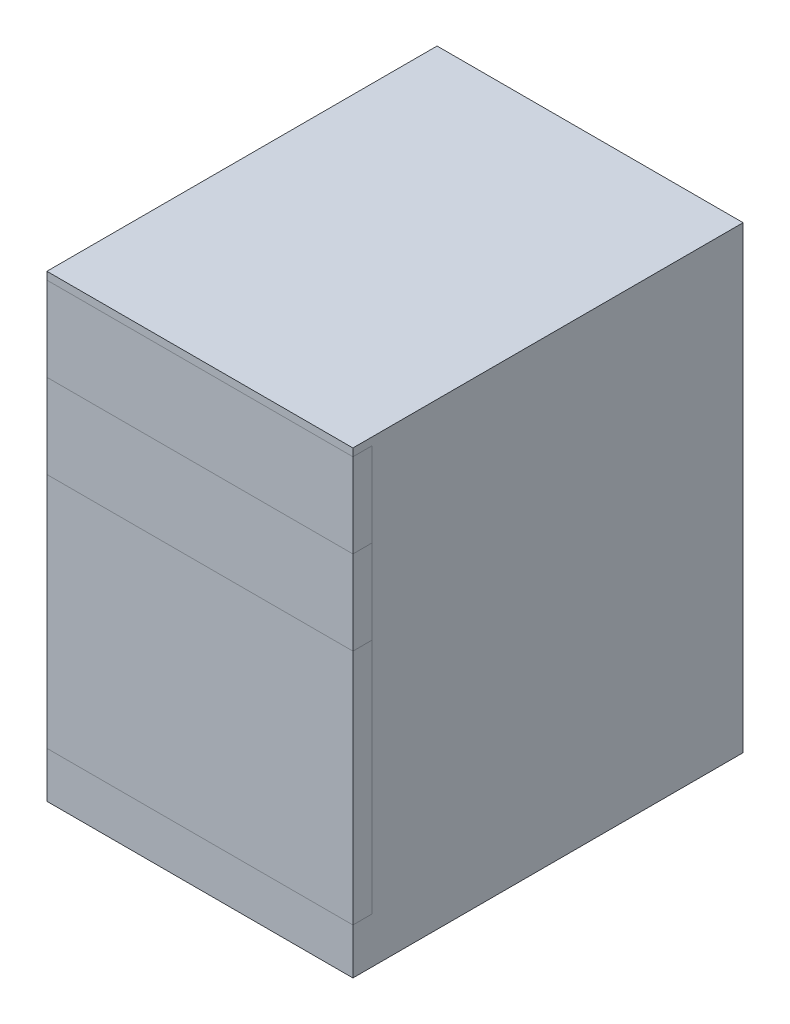
SolidWorks part; units mm, degrees
ref_plane "Front Plane" through (0, 0, 0) normal (0, 0, 1) x (1, 0, 0)
ref_plane "Top Plane" through (0, 0, 0) normal (0, 1, 0) x (1, 0, 0)
ref_plane "Right Plane" through (0, 0, 0) normal (1, 0, 0) x (0, 0, -1)
sketch "Sketch1" plane through (0, 0, 0) normal (0, 1, 0) x (1, 0, 0)
  line L1 (-200, -255) -> (200, -255)
  line L2 (-200, -255) -> (-200, 255)
  line L3 (-200, 255) -> (200, 255)
  line L4 (200, -255) -> (200, 255)
  line L5 (-200, -255) -> (200, 255) construction
  line L6 (-200, 255) -> (200, -255) construction
  point P0 (0, 0)
  dimension "D1" = 400
  dimension "D2" = 510
extrude "Boss-Extrude1" add sketch "Sketch1" along normal blind 600
sketch "Sketch2" plane through (0, 0, 255) normal (0, 0, 1) x (1, 0, 0)
  line L0 (200, 600) -> (200, 0) construction
  line L1 (-200, 600) -> (200, 600)
  line L2 (-200, 600) -> (-200, 590)
  line L3 (-200, 590) -> (200, 590)
  line L4 (200, 600) -> (200, 590)
  line L5 (-200, 600) -> (-200, 0) construction
  line L6 (200, 590) -> (-200, 590)
  line L7 (200, 590) -> (200, 480)
  line L8 (200, 480) -> (-200, 480)
  line L9 (-200, 590) -> (-200, 480)
  line L11 (-200, 480) -> (200, 480)
  line L12 (-200, 480) -> (-200, 370)
  line L13 (-200, 370) -> (200, 370)
  line L14 (200, 480) -> (200, 370)
  line L15 (200, 370) -> (-200, 370)
  line L16 (200, 370) -> (200, 60)
  line L17 (200, 60) -> (-200, 60)
  line L18 (-200, 370) -> (-200, 60)
  line M7 (200, 0) -> (200, 600)
  line M9 (-200, 600) -> (-200, 0)
  dimension "D1" = 10
  dimension "D2" = 110
  dimension "D3" = 110
  dimension "D4" = 310
extrude "Cut-Extrude1" cut sketch "Sketch2" against normal blind 25 contours L13 L8 M9 M7 | L8 L3 M7 M9 | L17 L13 M7 M9 region at (0, 535, 255) region at (0, 425, 255) region at (0, 215, 255)
extrude "Boss-Extrude3" add sketch "Sketch2<4>" along normal blind 25 from surface separate body contours L8 L3 M7 M9 region at (0, 535, 255) starting at face at (0, 325, 230)
sketch "Sketch2<4>" plane through (0, 0, 255) normal (0, 0, 1) x (1, 0, 0) same geometry as "Sketch2"
extrude "Boss-Extrude4" add sketch "Sketch2<5>" along normal blind 25 from surface separate body contours L13 L8 M9 M7 region at (0, 425, 255) starting at face at (0, 325, 230)
sketch "Sketch2<5>" plane through (0, 0, 255) normal (0, 0, 1) x (1, 0, 0) same geometry as "Sketch2"
extrude "Boss-Extrude5" add sketch "Sketch2<6>" along normal blind 25 from surface separate body contours L17 L13 M7 M9 region at (0, 215, 255) starting at face at (0, 325, 230)
sketch "Sketch2<6>" plane through (0, 0, 255) normal (0, 0, 1) x (1, 0, 0) same geometry as "Sketch2"
